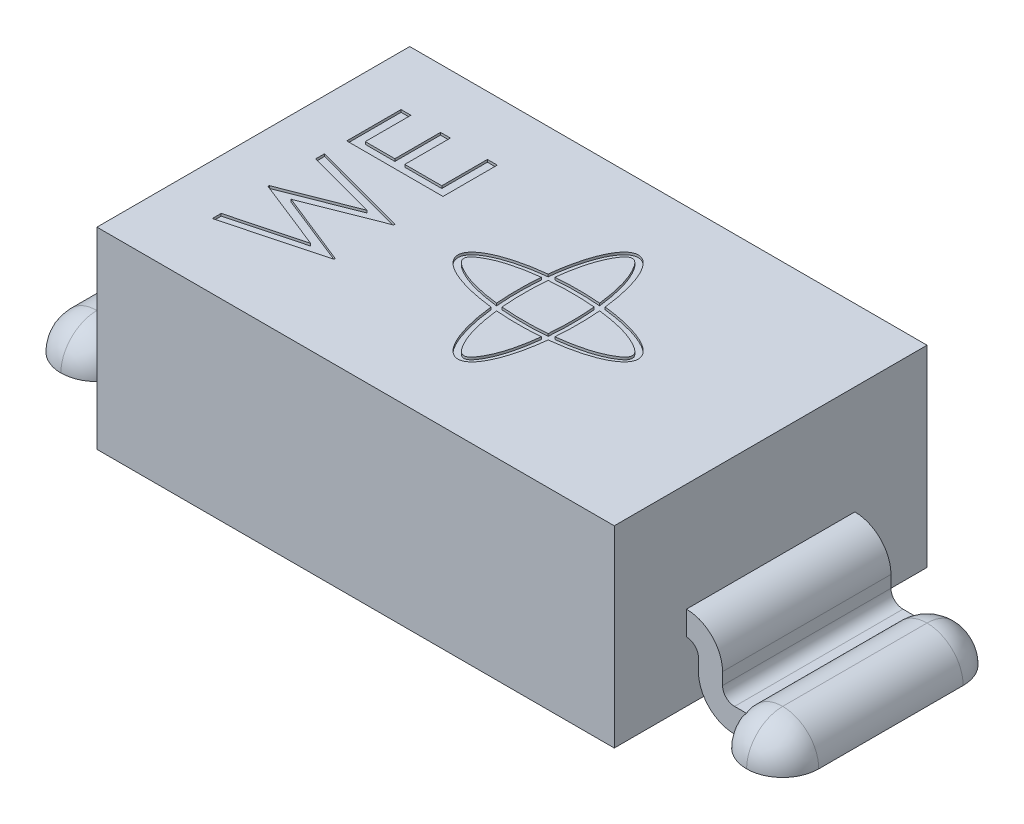
SolidWorks part; units mm, degrees
note: The reader was unsure of these and kept them because the rebuilt part matched: shared geometry of "Croquis3<2>".
ref_plane "Alzado" through (0, 0, 0) normal (0, 0, 1) x (1, 0, 0)
ref_plane "Planta" through (0, 0, 0) normal (0, 1, 0) x (1, 0, 0)
ref_plane "Vista lateral" through (0, 0, 0) normal (1, 0, 0) x (0, 0, -1)
sketch "Croquis1" plane through (0, 0, 0) normal (0, 1, 0) x (1, 0, 0)
  line L1 (-2.15, -1.3) -> (2.15, -1.3)
  line L2 (-2.15, -1.3) -> (-2.15, 1.3)
  line L3 (-2.15, 1.3) -> (2.15, 1.3)
  line L4 (2.15, -1.3) -> (2.15, 1.3)
  line L5 (-2.15, -1.3) -> (2.15, 1.3) construction
  line L6 (-2.15, 1.3) -> (2.15, -1.3) construction
  point P0 (0, 0)
  dimension "D1" = 4.3
  dimension "D2" = 2.6
extrude "Saliente-Extruir1" add sketch "Croquis1" along normal blind 1.6
sketch "Croquis2" plane through (0, 0, 0) normal (1, 0, 0) x (0, 0, -1)
  line L0 (-1.3, 1.6) -> (1.3, 1.6) construction
  line L1 (-0.7, 0.5) -> (0.7, 0.5)
  line L2 (-0.7, 0.5) -> (-0.7, 0.7)
  line L3 (-0.7, 0.7) -> (0.7, 0.7)
  line L4 (0.7, 0.5) -> (0.7, 0.7)
  line L5 (-0.7, 0.5) -> (0.7, 0.7) construction
  line L6 (-0.7, 0.7) -> (0.7, 0.5) construction
  point P0 (0, 0.6)
  dimension "D1" = 0.9
  dimension "D2" = 1.4
  dimension "D3" = 0.2
extrude "Cortar-Extruir1" cut sketch "Croquis2" against normal through all both and the other way through all
sketch "Croquis3" plane through (0, 0, 0) normal (0, 0, 1) x (1, 0, 0)
  line L0 (2.15, 0.5) -> (-2.15, 0.5)
  line L1 (-2.55, 0.2) -> (-3, 0.2)
  line L2 (2.25, 0.4) -> (2.25, 0.3)
  line L3 (2.55, 0) -> (3, 0)
  line L4 (0, 0) -> (0, 0.5) construction
  line L5 (-2.55, 0) -> (-3, 0)
  line L6 (-2.25, 0.4) -> (-2.25, 0.3)
  line L7 (-2.45, 0.4) -> (-2.45, 0.3)
  line L8 (2.15, 0.7) -> (-2.15, 0.7)
  line L9 (2.45, 0.4) -> (2.45, 0.3)
  line L10 (2.55, 0.2) -> (3, 0.2)
  line L11 (-3, 0) -> (-3, 0.2)
  line L12 (3, 0) -> (3, 0.2)
  arc A0 (2.15, 0.5) -> (2.25, 0.4) centre (2.15, 0.4) cw
  arc A1 (2.25, 0.3) -> (2.55, 0) centre (2.55, 0.3) ccw
  arc A2 (-2.25, 0.3) -> (-2.55, 0) centre (-2.55, 0.3) cw
  arc A3 (-2.15, 0.5) -> (-2.25, 0.4) centre (-2.15, 0.4) ccw
  arc A4 (-2.45, 0.3) -> (-2.55, 0.2) centre (-2.55, 0.3) cw
  arc A5 (-2.15, 0.7) -> (-2.45, 0.4) centre (-2.15, 0.4) ccw
  arc A6 (2.15, 0.7) -> (2.45, 0.4) centre (2.15, 0.4) cw
  arc A7 (2.45, 0.3) -> (2.55, 0.2) centre (2.55, 0.3) ccw
  point P3 (0, 0.5)
  dimension "D3" = 0.1
  dimension "D1" = 6
  dimension "D2" = 0.2
extrude "Saliente-Extruir2" add sketch "Croquis3" along normal mid plane 1.4 separate body
sketch "Croquis4" plane through (0, 0, 0) normal (0, 1, 0) x (1, 0, 0)
  line L0 (-2.85, 0) -> (0, 0) construction
  line L1 (-2.55, 0.9) -> (-3.15, 0.9)
  line L2 (-2.55, 0.9) -> (-2.55, -0.9)
  line L3 (-2.55, -0.9) -> (-3.15, -0.9)
  line L4 (-3.15, 0.9) -> (-3.15, -0.9)
  line L5 (-2.55, 0.9) -> (-3.15, -0.9) construction
  line L6 (-2.55, -0.9) -> (-3.15, 0.9) construction
  line L7 (0, 0) -> (0, -1.3) construction
  line L8 (-2.15, -1.3) -> (2.15, -1.3) construction
  line L9 (2.55, -0.9) -> (3.15, -0.9)
  line L10 (3.15, 0.9) -> (3.15, -0.9)
  line L11 (2.55, 0.9) -> (3.15, 0.9)
  line L12 (2.55, 0.9) -> (2.55, -0.9)
  point P0 (-2.85, 0)
  dimension "D1" = 0.6
  dimension "D2" = 1.8
extrude "Saliente-Extruir3" add sketch "Croquis4" along normal blind 0.3 separate body
fillet "Redondeo1" radius 0.3 2 edges at (-3.15, 0.3, 0) (-2.55, 0.3, 0)
fillet "Redondeo2" radius 0.3 2 edges at (3.15, 0.3, 0) (2.55, 0.3, 0)
extrude "Cortar-Extruir2" cut sketch "Croquis3<2>" against normal mid plane 1.4
sketch "Croquis3<2>" plane through (0, 0, 0) normal (0, 0, 1) x (1, 0, 0) same geometry as "Croquis3"
sketch "Croquis5" plane through (0, 1.6, 0) normal (0, 1, 0) x (1, 0, 0)
  line L0 (1.05, 0) -> (-0.45, 0) construction
  line L1 (0.3, -0.25) -> (0.3, 0.25) construction
  line L3 (-1.7325, -0.759) -> (-1.7325, -0.6848)
  line L4 (-1.7325, -0.6848) -> (-1.1458, -0.5282)
  line L5 (-1.1458, -0.5282) -> (-1.7325, -0.2954)
  line L6 (-1.7325, -0.2954) -> (-1.7325, -0.2849)
  line L7 (-1.7325, -0.2849) -> (-1.1498, -0.0564)
  line L8 (-1.1498, -0.0564) -> (-1.7325, 0.101)
  line L9 (-1.7325, 0.101) -> (-1.7325, 0.1744)
  line L10 (-1.7325, 0.1744) -> (-0.9325, -0.0413)
  line L11 (-0.9325, -0.0413) -> (-0.9325, -0.0516)
  line L12 (-0.9325, -0.0516) -> (-1.5443, -0.2923)
  line L13 (-1.5443, -0.2923) -> (-0.9325, -0.5359)
  line L14 (-0.9325, -0.5359) -> (-0.9325, -0.5462)
  line L15 (-0.9325, -0.5462) -> (-1.7325, -0.759)
  line L16 (-1.7325, 0.359) -> (-1.7325, 0.8103)
  line L17 (-1.7325, 0.8103) -> (-1.6504, 0.8103)
  line L18 (-1.6504, 0.8103) -> (-1.6504, 0.4308)
  line L19 (-1.6504, 0.4308) -> (-1.4043, 0.4308)
  line L20 (-1.4043, 0.4308) -> (-1.4043, 0.8103)
  line L21 (-1.4043, 0.8103) -> (-1.3222, 0.8103)
  line L22 (-1.3222, 0.8103) -> (-1.3222, 0.4308)
  line L23 (-1.3222, 0.4308) -> (-1.0145, 0.4308)
  line L24 (-1.0145, 0.4308) -> (-1.0145, 0.8103)
  line L25 (-1.0145, 0.8103) -> (-0.9325, 0.8103)
  line L26 (-0.9325, 0.8103) -> (-0.9325, 0.359)
  line L27 (-0.9325, 0.359) -> (-1.7325, 0.359)
  ellipse E0 centre (0.3, 0) end of major axis (-0.45, 0) minor radius 0.25 (0.0628, 0.2372) -> (0.0628, -0.2372) ccw
  ellipse E1 centre (0.3, 0) end of major axis (0.3, 0.75) minor radius 0.25 (0.0578, 0.1863) -> (0.0578, -0.1863) ccw
  ellipse E2 centre (0.3, 0) end of major axis (-0.45, 0) minor radius 0.25 (0.1137, -0.2422) -> (0.4863, -0.2422) ccw
  ellipse E3 centre (0.3, 0) end of major axis (0.3, 0.75) minor radius 0.25 (0.0628, -0.2372) -> (0.5372, -0.2372) ccw
  ellipse E4 centre (0.3, 0) end of major axis (-0.45, 0) minor radius 0.25 (0.5372, -0.2372) -> (0.5372, 0.2372) ccw
  ellipse E5 centre (0.3, 0) end of major axis (0.3, 0.75) minor radius 0.25 (0.5422, -0.1863) -> (0.5422, 0.1863) ccw
  ellipse E6 centre (0.3, 0) end of major axis (-0.45, 0) minor radius 0.25 (0.4863, 0.2422) -> (0.1137, 0.2422) ccw
  ellipse E7 centre (0.3, 0) end of major axis (0.3, 0.75) minor radius 0.25 (0.5372, 0.2372) -> (0.0628, 0.2372) ccw
  spline S0 degree 3 poles (0.1137, -0.2422) (0.1255, -0.3449) (0.1618, -0.5222) (0.2485, -0.6829) (0.3, -0.7086) (0.3515, -0.6829) (0.4382, -0.5222) (0.4745, -0.3449) (0.4863, -0.2422) knots 1.908725 1.908725 1.908725 1.908725 2.356194 2.748894 3.141593 3.534292 3.926991 4.37446 4.37446 4.37446 4.37446
  spline S1 degree 3 poles (0.0578, 0.1863) (0.0321, 0.1833) (-0.0689, 0.1694) (-0.2367, 0.1304) (-0.3829, 0.0515) (-0.4086, 0) (-0.3829, -0.0515) (-0.2222, -0.1382) (-0.0449, -0.1745) (0.0578, -0.1863) knots 5.04935 5.04935 5.04935 5.04935 5.161459 5.497787 5.890486 6.283185 6.675884 7.068583 7.516053 7.516053 7.516053 7.516053
  spline S2 degree 3 poles (0.1085, -0.1915) (0.1708, -0.1971) (0.3, -0.2029) (0.4292, -0.1971) (0.4915, -0.1915) knots 7.588701 7.588701 7.588701 7.588701 7.853982 8.119262 8.119262 8.119262 8.119262
  spline S3 degree 3 poles (0.1085, 0.1915) (0.1029, 0.1292) (0.0971, 0) (0.1029, -0.1292) (0.1085, -0.1915) knots 1.305515 1.305515 1.305515 1.305515 1.570796 1.836076 1.836076 1.836076 1.836076
  spline S4 degree 3 poles (0.4915, -0.1915) (0.4971, -0.1292) (0.5029, 0) (0.4971, 0.1292) (0.4915, 0.1915) knots 4.447109 4.447109 4.447109 4.447109 4.712389 4.977669 4.977669 4.977669 4.977669
  spline S5 degree 3 poles (0.5422, -0.1863) (0.6449, -0.1745) (0.8222, -0.1382) (0.9829, -0.0515) (1.0086, 0) (0.9829, 0.0515) (0.8222, 0.1382) (0.6449, 0.1745) (0.5422, 0.1863) knots 8.191911 8.191911 8.191911 8.191911 8.63938 9.032079 9.424778 9.817477 10.210176 10.657567 10.657567 10.657567 10.657567
  spline S6 degree 3 poles (0.4915, 0.1915) (0.4291, 0.1971) (0.3096, 0.2025) (0.1803, 0.1976) (0.1178, 0.1924) (0.1085, 0.1915) knots 10.730174 10.730174 10.730174 10.730174 10.995574 11.220426 11.259985 11.259985 11.259985 11.259985
  spline S7 degree 3 poles (0.4863, 0.2422) (0.4745, 0.3449) (0.4382, 0.5222) (0.3515, 0.6829) (0.3, 0.7086) (0.2485, 0.6829) (0.1618, 0.5222) (0.1255, 0.3449) (0.1137, 0.2422) knots 5.050318 5.050318 5.050318 5.050318 5.497787 5.890486 6.283185 6.675884 7.068583 7.516053 7.516053 7.516053 7.516053
  point P8 (0.3, 0)
  point P36 (0.3, 0)
extrude "Cortar-Extruir3" cut sketch "Croquis5" against normal blind 0.02
sketch "Croquis6" [suppressed] plane through (0, 1.6, 0) normal (0, 1, 0) x (1, 0, 0)
  line L5 (-1.8077, 0.5273) -> (-1.6126, 0.5273)
  line L6 (-1.5373, -0.4727) -> (-1.8077, -0.4727)
  line L7 (-1.8077, -0.4727) -> (-1.8077, 0.5273)
  line L8 (-1.7179, 0.4247) -> (-1.7179, 0.1042)
  line L9 (-1.7179, 0.1042) -> (-1.6577, 0.1042)
  line L10 (-1.5962, 0.4247) -> (-1.7179, 0.4247)
  line L11 (-1.7179, 0.0016) -> (-1.7179, -0.3702)
  line L12 (-1.7179, -0.3702) -> (-1.5901, -0.3702)
  line L13 (-1.6585, 0.0016) -> (-1.7179, 0.0016)
  line L14 (-0.9744, 0.2965) -> (-1.0641, 0.2965)
  line L15 (-1.1026, -0.2035) -> (-1.0128, -0.2035)
  line L16 (-0.8205, 0.0273) -> (-0.8205, 0.1298)
  line L17 (0.2125, 0.5529) -> (0.2308, 0.5529)
  line L18 (0.2308, 0.5529) -> (0.2308, -0.1394)
  line L19 (0.2308, -0.1394) -> (0.3462, -0.1394)
  line L20 (0.3462, -0.1394) -> (0.3462, -0.242)
  line L21 (0.3462, -0.242) -> (0.2308, -0.242)
  line L22 (0.2308, -0.242) -> (0.2308, -0.4727)
  line L23 (0.2308, -0.4727) -> (0.141, -0.4727)
  line L24 (0.141, -0.4727) -> (0.141, -0.242)
  line L25 (0.141, -0.242) -> (-0.3333, -0.242)
  line L26 (-0.3333, -0.242) -> (0.2125, 0.5529)
  line L27 (0.141, -0.1394) -> (0.141, 0.2949)
  line L28 (0.141, 0.2949) -> (-0.1571, -0.1394)
  line L29 (-0.1571, -0.1394) -> (0.141, -0.1394)
  line L30 (1.751, 0.5529) -> (1.7692, 0.5529)
  line L31 (1.7692, 0.5529) -> (1.7692, -0.1394)
  line L32 (1.7692, -0.1394) -> (1.8846, -0.1394)
  line L33 (1.8846, -0.1394) -> (1.8846, -0.242)
  line L34 (1.8846, -0.242) -> (1.7692, -0.242)
  line L35 (1.7692, -0.242) -> (1.7692, -0.4727)
  line L36 (1.7692, -0.4727) -> (1.6795, -0.4727)
  line L37 (1.6795, -0.4727) -> (1.6795, -0.242)
  line L38 (1.6795, -0.242) -> (1.2051, -0.242)
  line L39 (1.2051, -0.242) -> (1.751, 0.5529)
  line L40 (1.6795, -0.1394) -> (1.6795, 0.2949)
  line L41 (1.6795, 0.2949) -> (1.3814, -0.1394)
  line L42 (1.3814, -0.1394) -> (1.6795, -0.1394)
  spline S0 degree 3 poles (-1.6126, 0.5273) (-1.5941, 0.5274) (-1.5671, 0.5264) (-1.5324, 0.5236) (-1.5089, 0.5203) (-1.4871, 0.5164) (-1.4669, 0.5116) (-1.4484, 0.5059) (-1.4264, 0.4968) (-1.4013, 0.4832) (-1.3741, 0.4633) (-1.3508, 0.4388) (-1.3308, 0.4113) (-1.3149, 0.3809) (-1.2993, 0.3375) (-1.2947, 0.3028) (-1.2949, 0.2795) knots 0 0 0 0 0.121323 0.17668 0.228365 0.276868 0.321879 0.364099 0.403356 0.477968 0.550535 0.623584 0.698175 0.773354 0.847281 1 1 1 1
  spline S1 degree 3 poles (-1.2949, 0.2795) (-1.2947, 0.2578) (-1.2984, 0.2256) (-1.3109, 0.1848) (-1.3236, 0.1562) (-1.3402, 0.1299) (-1.3667, 0.0972) (-1.3925, 0.0781) (-1.4105, 0.0667) knots 0 0 0 0 0.256581 0.380552 0.503623 0.625739 0.747549 1 1 1 1
  spline S2 degree 3 poles (-1.4105, 0.0667) (-1.3887, 0.0587) (-1.3578, 0.0458) (-1.3217, 0.0232) (-1.2999, 0.0057) (-1.2812, -0.0132) (-1.2649, -0.0337) (-1.251, -0.0561) (-1.2391, -0.0803) (-1.2298, -0.1058) (-1.2203, -0.1418) (-1.2181, -0.17) (-1.2179, -0.1889) knots 0 0 0 0 0.202914 0.2903 0.370223 0.446384 0.521397 0.598291 0.676142 0.755529 0.834887 1 1 1 1
  spline S3 degree 3 poles (-1.2179, -0.1889) (-1.2181, -0.208) (-1.2204, -0.2366) (-1.2297, -0.273) (-1.2391, -0.2989) (-1.2515, -0.3237) (-1.2665, -0.3473) (-1.2844, -0.3696) (-1.3044, -0.3909) (-1.327, -0.41) (-1.3515, -0.427) (-1.378, -0.441) (-1.4062, -0.4527) (-1.4363, -0.4617) (-1.48, -0.4703) (-1.5141, -0.473) (-1.5373, -0.4727) knots 0 0 0 0 0.120335 0.17818 0.235235 0.292683 0.351186 0.410457 0.47172 0.533761 0.595739 0.657888 0.721295 0.786823 0.854686 1 1 1 1
  spline S4 degree 3 poles (-1.6577, 0.1042) (-1.6406, 0.1045) (-1.6159, 0.1045) (-1.5843, 0.1069) (-1.5632, 0.1087) (-1.5439, 0.1116) (-1.5266, 0.115) (-1.5108, 0.1186) (-1.4927, 0.1248) (-1.4721, 0.1339) (-1.4501, 0.148) (-1.4308, 0.1649) (-1.4144, 0.1843) (-1.4011, 0.2057) (-1.3885, 0.2365) (-1.3842, 0.2611) (-1.3846, 0.2777) knots 0 0 0 0 0.1397 0.202289 0.2606 0.31319 0.361739 0.405706 0.44554 0.518832 0.589778 0.658867 0.72843 0.797283 0.864815 1 1 1 1
  spline S5 degree 3 poles (-1.3846, 0.2777) (-1.3847, 0.2885) (-1.386, 0.3046) (-1.3916, 0.3249) (-1.3969, 0.3391) (-1.4042, 0.3521) (-1.4129, 0.3644) (-1.4234, 0.3755) (-1.4353, 0.3859) (-1.449, 0.3951) (-1.4645, 0.4032) (-1.482, 0.4097) (-1.5012, 0.4154) (-1.5223, 0.4194) (-1.554, 0.424) (-1.579, 0.4246) (-1.5962, 0.4247) knots 0 0 0 0 0.111818 0.164402 0.21587 0.266841 0.317479 0.369902 0.4234 0.479718 0.539241 0.602431 0.67103 0.744485 0.823454 1 1 1 1
  spline S6 degree 3 poles (-1.5901, -0.3702) (-1.5725, -0.3699) (-1.547, -0.3697) (-1.5143, -0.3676) (-1.4927, -0.3651) (-1.4728, -0.3624) (-1.4549, -0.3588) (-1.4388, -0.3547) (-1.4202, -0.3483) (-1.3991, -0.3384) (-1.3765, -0.3235) (-1.3564, -0.3056) (-1.3393, -0.285) (-1.3253, -0.2626) (-1.3117, -0.2311) (-1.3077, -0.2057) (-1.3077, -0.1889) knots 0 0 0 0 0.139739 0.201795 0.259822 0.312206 0.360773 0.40454 0.443698 0.516841 0.587874 0.657965 0.728969 0.799308 0.866636 1 1 1 1
  spline S7 degree 3 poles (-1.3077, -0.1889) (-1.3075, -0.1784) (-1.3091, -0.1628) (-1.3137, -0.1428) (-1.3182, -0.1283) (-1.3246, -0.1145) (-1.3322, -0.1012) (-1.341, -0.0882) (-1.3548, -0.0719) (-1.3748, -0.0531) (-1.4139, -0.0277) (-1.4477, -0.0157) (-1.4714, -0.0102) knots 0 0 0 0 0.119602 0.177503 0.235143 0.292133 0.350871 0.410098 0.470732 0.594829 0.722579 1 1 1 1
  spline S8 degree 3 poles (-1.4714, -0.0102) (-1.4819, -0.0078) (-1.499, -0.0053) (-1.5236, -0.0028) (-1.5457, -0.0013) (-1.5704, 0.0002) (-1.6082, 0.0011) (-1.6379, 0.0018) (-1.6585, 0.0016) knots 0 0 0 0 0.171953 0.277057 0.394731 0.526177 0.671345 1 1 1 1
  spline S9 degree 3 poles (-1.0641, 0.2965) (-1.0599, 0.3163) (-1.0509, 0.3448) (-1.0362, 0.381) (-1.0232, 0.4056) (-1.0091, 0.4287) (-0.9929, 0.4497) (-0.9754, 0.4693) (-0.956, 0.4866) (-0.9357, 0.5023) (-0.9141, 0.5157) (-0.8918, 0.5272) (-0.8685, 0.5367) (-0.8441, 0.5439) (-0.8102, 0.5509) (-0.7841, 0.5531) (-0.7664, 0.5529) knots 0 0 0 0 0.141977 0.208985 0.273957 0.336889 0.398745 0.460116 0.520825 0.580994 0.640152 0.698622 0.757271 0.816427 0.876254 1 1 1 1
  spline S10 degree 3 poles (-0.7664, 0.5529) (-0.7406, 0.5531) (-0.7021, 0.5486) (-0.653, 0.5334) (-0.6182, 0.5178) (-0.5859, 0.4986) (-0.5571, 0.4758) (-0.5323, 0.4497) (-0.5114, 0.4209) (-0.4951, 0.3902) (-0.4791, 0.3482) (-0.4744, 0.315) (-0.4744, 0.2931) knots 0 0 0 0 0.17854 0.266093 0.354631 0.441886 0.525747 0.608114 0.690197 0.770821 0.848326 1 1 1 1
  spline S11 degree 3 poles (-0.4744, 0.2931) (-0.4744, 0.2725) (-0.4775, 0.2417) (-0.4902, 0.2032) (-0.503, 0.1763) (-0.5197, 0.1513) (-0.5473, 0.1193) (-0.5728, 0.0993) (-0.5911, 0.0874) knots 0 0 0 0 0.250608 0.37063 0.490072 0.610375 0.734313 1 1 1 1
  spline S12 degree 3 poles (-0.5911, 0.0874) (-0.5698, 0.0779) (-0.5293, 0.0542) (-0.4966, 0.0205) (-0.4828, 0.002) knots 0 0 0 0 0.503009 1 1 1 1
  spline S13 degree 3 poles (-0.4828, 0.002) (-0.4728, -0.0107) (-0.4603, -0.0313) (-0.446, -0.0599) (-0.4376, -0.0819) (-0.4312, -0.1045) (-0.425, -0.1356) (-0.4232, -0.1596) (-0.4231, -0.1756) knots 0 0 0 0 0.254173 0.378112 0.501712 0.623986 0.747096 1 1 1 1
  spline S14 degree 3 poles (-0.4231, -0.1756) (-0.4229, -0.2036) (-0.429, -0.2456) (-0.448, -0.2992) (-0.4681, -0.3378) (-0.4926, -0.3739) (-0.5218, -0.4062) (-0.5553, -0.434) (-0.5927, -0.4572) (-0.6332, -0.4757) (-0.6917, -0.4932) (-0.7378, -0.4986) (-0.769, -0.4984) knots 0 0 0 0 0.158922 0.239619 0.322609 0.406035 0.487602 0.569685 0.653036 0.737436 0.822478 1 1 1 1
  spline S15 degree 3 poles (-0.769, -0.4984) (-0.79, -0.4981) (-0.8212, -0.4965) (-0.8612, -0.4882) (-0.8894, -0.48) (-0.9162, -0.4696) (-0.9416, -0.4566) (-0.9657, -0.4414) (-0.9883, -0.4237) (-1.0094, -0.4039) (-1.0285, -0.3817) (-1.0458, -0.3574) (-1.061, -0.3308) (-1.0746, -0.3022) (-1.0899, -0.26) (-1.0985, -0.2266) (-1.1026, -0.2035) knots 0 0 0 0 0.128963 0.190377 0.250092 0.308548 0.366398 0.424542 0.48317 0.542243 0.601739 0.662506 0.724856 0.789128 0.856346 1 1 1 1
  spline S16 degree 3 poles (-1.0128, -0.2035) (-1.0083, -0.2185) (-1.0015, -0.2404) (-0.9894, -0.2675) (-0.9799, -0.2856) (-0.97, -0.3022) (-0.9555, -0.3215) (-0.9435, -0.3345) (-0.9345, -0.3417) knots 0 0 0 0 0.291316 0.425966 0.55216 0.671527 0.786122 1 1 1 1
  spline S17 degree 3 poles (-0.9345, -0.3417) (-0.9235, -0.3506) (-0.9059, -0.3625) (-0.8803, -0.3752) (-0.8598, -0.3825) (-0.8384, -0.3886) (-0.8075, -0.3941) (-0.7837, -0.396) (-0.7674, -0.3958) knots 0 0 0 0 0.236178 0.355663 0.475904 0.600127 0.728608 1 1 1 1
  spline S18 degree 3 poles (-0.7674, -0.3958) (-0.7491, -0.3959) (-0.7223, -0.3938) (-0.6877, -0.3875) (-0.6638, -0.3804) (-0.6413, -0.3716) (-0.6203, -0.3605) (-0.6007, -0.3476) (-0.5826, -0.3329) (-0.5663, -0.3167) (-0.552, -0.2999) (-0.5398, -0.2824) (-0.53, -0.2641) (-0.5222, -0.2451) (-0.5151, -0.2186) (-0.5125, -0.1981) (-0.5128, -0.1843) knots 0 0 0 0 0.148752 0.218403 0.28576 0.350598 0.414964 0.478069 0.541761 0.60435 0.664075 0.721464 0.777587 0.832644 0.887844 1 1 1 1
  spline S19 degree 3 poles (-0.5128, -0.1843) (-0.5129, -0.1657) (-0.5171, -0.1376) (-0.5318, -0.1027) (-0.5471, -0.0778) (-0.5657, -0.0547) (-0.5876, -0.0341) (-0.6127, -0.0171) (-0.6359, -0.0054) (-0.6564, 0.0027) (-0.6739, 0.008) (-0.6936, 0.0125) (-0.7151, 0.0167) (-0.7386, 0.0203) (-0.7739, 0.0244) (-0.8015, 0.0263) (-0.8205, 0.0273) knots 0 0 0 0 0.133485 0.201035 0.271234 0.34288 0.413836 0.485977 0.56023 0.599884 0.644055 0.691892 0.744688 0.801492 0.862858 1 1 1 1
  spline S20 degree 3 poles (-0.8205, 0.1298) (-0.7963, 0.1295) (-0.7606, 0.1329) (-0.7147, 0.1423) (-0.6831, 0.1529) (-0.6544, 0.1651) (-0.6294, 0.1793) (-0.6086, 0.1952) (-0.5921, 0.2128) (-0.5797, 0.2318) (-0.5675, 0.258) (-0.5642, 0.2794) (-0.5641, 0.2935) knots 0 0 0 0 0.215787 0.318027 0.417574 0.51165 0.596162 0.672935 0.74367 0.810677 0.874059 1 1 1 1
  spline S21 degree 3 poles (-0.5641, 0.2935) (-0.5639, 0.3039) (-0.5659, 0.3193) (-0.5719, 0.339) (-0.578, 0.3532) (-0.5862, 0.3668) (-0.5961, 0.3798) (-0.6078, 0.3923) (-0.6212, 0.4039) (-0.6356, 0.415) (-0.6514, 0.4244) (-0.6681, 0.4324) (-0.6857, 0.4391) (-0.7043, 0.444) (-0.7308, 0.4489) (-0.7513, 0.4503) (-0.7652, 0.4504) knots 0 0 0 0 0.109966 0.163247 0.218076 0.273301 0.330909 0.390995 0.454176 0.518862 0.583311 0.648517 0.715031 0.782502 0.852323 1 1 1 1
  spline S22 degree 3 poles (-0.7652, 0.4504) (-0.7874, 0.4504) (-0.8202, 0.4464) (-0.8607, 0.4315) (-0.8835, 0.4186) (-0.9003, 0.4058) (-0.9123, 0.3946) (-0.9242, 0.3822) (-0.935, 0.3678) (-0.9459, 0.3524) (-0.9596, 0.3287) (-0.9687, 0.3098) (-0.9744, 0.2965) knots 0 0 0 0 0.239685 0.351816 0.463766 0.520818 0.579448 0.640604 0.705298 0.773634 0.844669 1 1 1 1
  spline S23 degree 3 poles (0.4359, 0.0269) (0.4358, 0.058) (0.4369, 0.1034) (0.4416, 0.162) (0.4462, 0.2017) (0.4518, 0.2387) (0.4593, 0.2728) (0.4678, 0.3041) (0.4777, 0.3328) (0.4888, 0.3592) (0.5009, 0.3839) (0.5145, 0.4068) (0.5288, 0.4283) (0.5443, 0.448) (0.5607, 0.4662) (0.5785, 0.4824) (0.5972, 0.4972) (0.617, 0.5102) (0.6371, 0.5217) (0.6579, 0.5314) (0.6794, 0.5391) (0.7013, 0.5455) (0.7315, 0.5513) (0.7547, 0.553) (0.7702, 0.5529) knots 0 0 0 0 0.133246 0.194313 0.251279 0.304513 0.354235 0.400481 0.443411 0.484015 0.523252 0.561042 0.5979 0.633518 0.668314 0.702496 0.736685 0.770293 0.803437 0.835913 0.86846 0.900847 0.933467 1 1 1 1
  spline S24 degree 3 poles (0.7702, 0.5529) (0.786, 0.553) (0.8096, 0.5514) (0.8402, 0.5454) (0.8624, 0.5392) (0.8842, 0.5314) (0.9053, 0.5216) (0.9259, 0.5103) (0.9457, 0.497) (0.965, 0.4821) (0.9831, 0.4653) (1.0001, 0.4468) (1.0163, 0.4267) (1.0312, 0.4046) (1.0454, 0.3809) (1.058, 0.3553) (1.0702, 0.3281) (1.0808, 0.2986) (1.0903, 0.2669) (1.098, 0.2328) (1.1044, 0.1963) (1.1093, 0.1573) (1.1143, 0.1006) (1.1151, 0.0568) (1.1154, 0.0269) knots 0 0 0 0 0.067194 0.099862 0.132567 0.165151 0.197913 0.231319 0.265083 0.299255 0.334399 0.369943 0.406284 0.444064 0.482998 0.523354 0.565537 0.609613 0.656391 0.705885 0.758325 0.813832 0.872795 1 1 1 1
  spline S25 degree 3 poles (1.1154, 0.0269) (1.1151, -0.0029) (1.1143, -0.0466) (1.1093, -0.1029) (1.1046, -0.1417) (1.0982, -0.178) (1.0903, -0.212) (1.0816, -0.2437) (1.0708, -0.2729) (1.0589, -0.3) (1.046, -0.3253) (1.0323, -0.3491) (1.0172, -0.3711) (1.0012, -0.3915) (0.9839, -0.4099) (0.9657, -0.4268) (0.9464, -0.4419) (0.9263, -0.455) (0.9057, -0.4668) (0.8844, -0.4763) (0.8627, -0.4845) (0.8404, -0.4907) (0.8096, -0.4965) (0.7861, -0.4986) (0.7702, -0.4984) knots 0 0 0 0 0.126773 0.185516 0.240765 0.29298 0.34225 0.388919 0.432776 0.474628 0.514775 0.553606 0.591426 0.628028 0.663804 0.698984 0.733591 0.767628 0.801208 0.834264 0.866981 0.89972 0.932702 1 1 1 1
  spline S26 degree 3 poles (0.7702, -0.4984) (0.7547, -0.4984) (0.7315, -0.4968) (0.7014, -0.4909) (0.6796, -0.4848) (0.6582, -0.4773) (0.6376, -0.4675) (0.6176, -0.4563) (0.598, -0.4435) (0.5795, -0.4288) (0.5617, -0.4126) (0.5453, -0.3944) (0.5299, -0.3746) (0.5154, -0.3532) (0.502, -0.3301) (0.4896, -0.3053) (0.4783, -0.2786) (0.4682, -0.2497) (0.4593, -0.2183) (0.4523, -0.1839) (0.4463, -0.147) (0.4415, -0.1074) (0.437, -0.0492) (0.4358, -0.0041) (0.4359, 0.0269) knots 0 0 0 0 0.066622 0.099285 0.131361 0.163585 0.196104 0.228902 0.262158 0.295991 0.330218 0.36506 0.400951 0.43762 0.475708 0.515381 0.556414 0.599765 0.646424 0.696431 0.749782 0.806573 0.867436 1 1 1 1
  spline S27 degree 3 poles (0.5256, 0.0273) (0.5254, 0.0014) (0.5266, -0.0363) (0.5298, -0.0848) (0.5329, -0.1174) (0.5374, -0.1475) (0.5424, -0.1751) (0.5486, -0.2002) (0.5559, -0.223) (0.5642, -0.2437) (0.5732, -0.2631) (0.583, -0.2812) (0.5939, -0.2979) (0.6057, -0.3133) (0.6183, -0.3276) (0.632, -0.3404) (0.651, -0.3558) (0.6761, -0.3716) (0.7178, -0.39) (0.7512, -0.3958) (0.7732, -0.3958) knots 0 0 0 0 0.141584 0.205926 0.265301 0.320597 0.371817 0.41879 0.461699 0.502134 0.540804 0.578181 0.614297 0.649678 0.684299 0.718359 0.752081 0.817652 0.879722 1 1 1 1
  spline S28 degree 3 poles (0.7732, -0.3958) (0.7954, -0.3962) (0.8286, -0.3901) (0.8701, -0.3723) (0.8947, -0.3567) (0.9134, -0.3417) (0.9268, -0.329) (0.9391, -0.3147) (0.9508, -0.2993) (0.9615, -0.2825) (0.9748, -0.2577) (0.9829, -0.2378) (0.9878, -0.2241) knots 0 0 0 0 0.225394 0.339595 0.459675 0.521735 0.583926 0.648174 0.713881 0.781004 0.851451 1 1 1 1
  spline S29 degree 3 poles (0.9878, -0.2241) (0.994, -0.2061) (1.0029, -0.1782) (1.011, -0.1395) (1.0166, -0.1088) (1.0204, -0.0767) (1.0246, -0.0312) (1.0256, 0.0036) (1.0256, 0.0273) knots 0 0 0 0 0.224542 0.342503 0.464324 0.590756 0.722227 1 1 1 1
  spline S30 degree 3 poles (1.0256, 0.0273) (1.0252, 0.0508) (1.0251, 0.0853) (1.021, 0.13) (1.0176, 0.1611) (1.0126, 0.1904) (1.0073, 0.2183) (1.0001, 0.2443) (0.9924, 0.2688) (0.9836, 0.2916) (0.9739, 0.3128) (0.9635, 0.3324) (0.9523, 0.3505) (0.9403, 0.3671) (0.9272, 0.3818) (0.9136, 0.3952) (0.8945, 0.4105) (0.8695, 0.426) (0.8284, 0.4451) (0.795, 0.4501) (0.7732, 0.4504) knots 0 0 0 0 0.128486 0.188175 0.245106 0.299448 0.350823 0.399942 0.446672 0.491255 0.533376 0.573853 0.612526 0.649597 0.685532 0.720106 0.753838 0.818925 0.880493 1 1 1 1
  spline S31 degree 3 poles (0.7732, 0.4504) (0.7512, 0.4501) (0.7174, 0.4451) (0.676, 0.4261) (0.6511, 0.4104) (0.632, 0.3955) (0.6185, 0.3825) (0.6059, 0.3683) (0.5943, 0.3528) (0.5834, 0.3361) (0.5734, 0.3181) (0.5644, 0.2987) (0.5561, 0.2779) (0.5488, 0.2552) (0.5428, 0.2301) (0.5372, 0.2026) (0.5332, 0.1724) (0.5297, 0.1397) (0.5266, 0.0911) (0.5254, 0.0533) (0.5256, 0.0273) knots 0 0 0 0 0.120883 0.182755 0.247811 0.281299 0.315088 0.349702 0.384857 0.420966 0.458511 0.497175 0.537602 0.580503 0.627468 0.678388 0.733983 0.793747 0.857714 1 1 1 1
extrude "Cortar-Extruir4" [suppressed] cut sketch "Croquis6" against normal blind 0.02
sketch "Croquis7" [suppressed] plane through (0, 1.6, 0) normal (0, 1, 0) x (1, 0, 0)
  line L1 (-1.7421, -0.3966) -> (-1.6407, -0.3358)
  line L2 (-1.0498, 0.3995) -> (-1.1472, 0.3257)
  line L3 (-0.9114, -0.3966) -> (-0.8099, -0.3358)
  line L4 (-0.2191, 0.3995) -> (-0.3164, 0.3257)
  line L5 (0.0886, 0.2949) -> (-0.0191, 0.2949)
  line L6 (-0.0652, -0.3051) -> (0.0425, -0.3051)
  line L7 (0.2732, -0.0281) -> (0.2732, 0.0949)
  line L8 (1.5129, 0.6026) -> (1.5348, 0.6026)
  line L9 (1.5348, 0.6026) -> (1.5348, -0.2281)
  line L10 (1.5348, -0.2281) -> (1.6732, -0.2281)
  line L11 (1.6732, -0.2281) -> (1.6732, -0.3512)
  line L12 (1.6732, -0.3512) -> (1.5348, -0.3512)
  line L13 (1.5348, -0.3512) -> (1.5348, -0.6281)
  line L14 (1.5348, -0.6281) -> (1.4271, -0.6281)
  line L15 (1.4271, -0.6281) -> (1.4271, -0.3512)
  line L16 (1.4271, -0.3512) -> (0.8579, -0.3512)
  line L17 (0.8579, -0.3512) -> (1.5129, 0.6026)
  line L18 (1.4271, -0.2281) -> (1.4271, 0.293)
  line L19 (1.4271, 0.293) -> (1.0694, -0.2281)
  line L20 (1.0694, -0.2281) -> (1.4271, -0.2281)
  spline S0 degree 3 poles (-1.6407, -0.3358) (-1.6231, -0.3663) (-1.5954, -0.4091) (-1.5518, -0.4575) (-1.5192, -0.4859) (-1.4855, -0.5083) (-1.4392, -0.5293) (-1.4019, -0.5359) (-1.3772, -0.5358) knots 0 0 0 0 0.304646 0.438547 0.562322 0.677433 0.786897 1 1 1 1
  spline S1 degree 3 poles (-1.3772, -0.5358) (-1.3564, -0.536) (-1.3253, -0.5323) (-1.2853, -0.5208) (-1.257, -0.5085) (-1.2306, -0.4937) (-1.2074, -0.4757) (-1.1874, -0.4556) (-1.171, -0.4332) (-1.1584, -0.4091) (-1.1455, -0.3762) (-1.1425, -0.3498) (-1.1421, -0.3325) knots 0 0 0 0 0.18093 0.270088 0.360156 0.448343 0.532666 0.613834 0.693982 0.772716 0.849335 1 1 1 1
  spline S2 degree 3 poles (-1.1421, -0.3325) (-1.142, -0.3121) (-1.1502, -0.2697) (-1.1721, -0.2326) (-1.1852, -0.2147) knots 0 0 0 0 0.477158 1 1 1 1
  spline S3 degree 3 poles (-1.1852, -0.2147) (-1.1962, -0.2001) (-1.2149, -0.178) (-1.244, -0.1497) (-1.2693, -0.1261) (-1.2982, -0.102) (-1.3416, -0.0665) (-1.3771, -0.0409) (-1.4015, -0.0233) knots 0 0 0 0 0.18953 0.299198 0.418926 0.548376 0.688136 1 1 1 1
  spline S4 degree 3 poles (-1.4015, -0.0233) (-1.4258, -0.0063) (-1.4598, 0.0189) (-1.5022, 0.0517) (-1.5287, 0.0731) (-1.5515, 0.0925) (-1.5751, 0.1136) (-1.5899, 0.1297) (-1.5982, 0.1399) knots 0 0 0 0 0.347082 0.495568 0.628357 0.74552 0.845831 1 1 1 1
  spline S5 degree 3 poles (-1.5982, 0.1399) (-1.6088, 0.1536) (-1.6236, 0.1747) (-1.6394, 0.2048) (-1.6485, 0.2276) (-1.6563, 0.2506) (-1.6632, 0.2822) (-1.6653, 0.3064) (-1.6652, 0.3226) knots 0 0 0 0 0.262559 0.388264 0.512667 0.633722 0.755394 1 1 1 1
  spline S6 degree 3 poles (-1.6652, 0.3226) (-1.6653, 0.3477) (-1.6605, 0.3851) (-1.6446, 0.4321) (-1.628, 0.4652) (-1.6067, 0.4953) (-1.582, 0.523) (-1.5526, 0.5462) (-1.5203, 0.5665) (-1.4849, 0.5824) (-1.4352, 0.5985) (-1.3957, 0.6023) (-1.3695, 0.6026) knots 0 0 0 0 0.16578 0.24628 0.327461 0.408797 0.489715 0.571376 0.655523 0.741019 0.826547 1 1 1 1
  spline S7 degree 3 poles (-1.3695, 0.6026) (-1.3415, 0.6027) (-1.2993, 0.5975) (-1.2461, 0.5788) (-1.2141, 0.563) (-1.189, 0.5471) (-1.1699, 0.5327) (-1.1505, 0.5161) (-1.1307, 0.4973) (-1.1108, 0.4761) (-1.083, 0.4439) (-1.0629, 0.4179) (-1.0498, 0.3995) knots 0 0 0 0 0.213252 0.31883 0.426794 0.483646 0.543604 0.608308 0.677127 0.750686 0.828713 1 1 1 1
  spline S8 degree 3 poles (-1.1472, 0.3257) (-1.1583, 0.3404) (-1.1753, 0.3611) (-1.1978, 0.3869) (-1.2137, 0.4032) (-1.2286, 0.4178) (-1.2431, 0.4303) (-1.2569, 0.4409) (-1.2742, 0.4521) (-1.2961, 0.4633) (-1.3329, 0.476) (-1.3621, 0.4794) (-1.3816, 0.4796) knots 0 0 0 0 0.189629 0.274184 0.352183 0.423199 0.488551 0.548473 0.60144 0.701198 0.799592 1 1 1 1
  spline S9 degree 3 poles (-1.3816, 0.4796) (-1.4054, 0.4799) (-1.4405, 0.4748) (-1.4824, 0.4558) (-1.5086, 0.4365) (-1.5304, 0.4136) (-1.5517, 0.3784) (-1.5575, 0.3478) (-1.5575, 0.3276) knots 0 0 0 0 0.275903 0.402371 0.528414 0.650356 0.765895 1 1 1 1
  spline S10 degree 3 poles (-1.5575, 0.3276) (-1.5579, 0.3147) (-1.555, 0.2955) (-1.5485, 0.2704) (-1.5409, 0.2515) (-1.5303, 0.2325) (-1.5107, 0.2048) (-1.4919, 0.1856) (-1.4784, 0.1726) knots 0 0 0 0 0.214746 0.322939 0.434116 0.553412 0.686073 1 1 1 1
  spline S11 degree 3 poles (-1.4784, 0.1726) (-1.4723, 0.1669) (-1.461, 0.1577) (-1.4431, 0.1443) (-1.4248, 0.1304) (-1.4028, 0.1143) (-1.3665, 0.0884) (-1.3377, 0.0676) (-1.3171, 0.0531) knots 0 0 0 0 0.124952 0.218094 0.333502 0.468789 0.624938 1 1 1 1
  spline S12 degree 3 poles (-1.3171, 0.0531) (-1.2919, 0.0348) (-1.2554, 0.008) (-1.2105, -0.0292) (-1.1812, -0.0554) (-1.1548, -0.0806) (-1.1317, -0.1052) (-1.1116, -0.1289) (-1.0899, -0.1592) (-1.0678, -0.1965) (-1.0428, -0.2563) (-1.0345, -0.3033) (-1.0345, -0.3341) knots 0 0 0 0 0.187773 0.272396 0.351321 0.424335 0.491909 0.554233 0.611268 0.716348 0.81454 1 1 1 1
  spline S13 degree 3 poles (-1.0345, -0.3341) (-1.0341, -0.3555) (-1.0376, -0.387) (-1.0478, -0.4279) (-1.0591, -0.457) (-1.0729, -0.4854) (-1.0905, -0.5122) (-1.1108, -0.5382) (-1.1341, -0.5626) (-1.1596, -0.5851) (-1.1866, -0.605) (-1.2151, -0.6216) (-1.2449, -0.6352) (-1.2761, -0.6458) (-1.32, -0.6562) (-1.3542, -0.659) (-1.3772, -0.6589) knots 0 0 0 0 0.121775 0.18092 0.240256 0.300114 0.361146 0.423501 0.488669 0.553954 0.617581 0.680238 0.742187 0.804663 0.868259 1 1 1 1
  spline S14 degree 3 poles (-1.3772, -0.6589) (-1.3953, -0.659) (-1.422, -0.6568) (-1.4571, -0.6509) (-1.4823, -0.644) (-1.507, -0.6356) (-1.5311, -0.6253) (-1.5545, -0.6129) (-1.5774, -0.5988) (-1.5997, -0.5823) (-1.6213, -0.5631) (-1.6428, -0.5417) (-1.6636, -0.5176) (-1.6841, -0.4911) (-1.7114, -0.4511) (-1.7301, -0.419) (-1.7421, -0.3966) knots 0 0 0 0 0.113696 0.169178 0.224159 0.27872 0.333794 0.389241 0.445822 0.503704 0.564294 0.627975 0.695038 0.765373 0.839611 1 1 1 1
  spline S15 degree 3 poles (-0.8099, -0.3358) (-0.7924, -0.3663) (-0.7646, -0.4091) (-0.721, -0.4575) (-0.6885, -0.4859) (-0.6548, -0.5083) (-0.6085, -0.5293) (-0.5712, -0.5359) (-0.5465, -0.5358) knots 0 0 0 0 0.304646 0.438547 0.562322 0.677433 0.786897 1 1 1 1
  spline S16 degree 3 poles (-0.5465, -0.5358) (-0.5256, -0.536) (-0.4945, -0.5323) (-0.4546, -0.5208) (-0.4262, -0.5085) (-0.3998, -0.4937) (-0.3766, -0.4757) (-0.3566, -0.4556) (-0.3402, -0.4332) (-0.3276, -0.4091) (-0.3147, -0.3762) (-0.3117, -0.3498) (-0.3114, -0.3325) knots 0 0 0 0 0.18093 0.270088 0.360156 0.448343 0.532666 0.613834 0.693982 0.772716 0.849335 1 1 1 1
  spline S17 degree 3 poles (-0.3114, -0.3325) (-0.3113, -0.3121) (-0.3195, -0.2697) (-0.3413, -0.2326) (-0.3544, -0.2147) knots 0 0 0 0 0.477158 1 1 1 1
  spline S18 degree 3 poles (-0.3544, -0.2147) (-0.3655, -0.2001) (-0.3842, -0.178) (-0.4132, -0.1497) (-0.4385, -0.1261) (-0.4674, -0.102) (-0.5109, -0.0665) (-0.5463, -0.0409) (-0.5707, -0.0233) knots 0 0 0 0 0.18953 0.299198 0.418926 0.548376 0.688136 1 1 1 1
  spline S19 degree 3 poles (-0.5707, -0.0233) (-0.595, -0.0063) (-0.629, 0.0189) (-0.6715, 0.0517) (-0.6979, 0.0731) (-0.7207, 0.0925) (-0.7444, 0.1136) (-0.7591, 0.1297) (-0.7674, 0.1399) knots 0 0 0 0 0.347082 0.495568 0.628357 0.74552 0.845831 1 1 1 1
  spline S20 degree 3 poles (-0.7674, 0.1399) (-0.778, 0.1536) (-0.7928, 0.1747) (-0.8086, 0.2048) (-0.8178, 0.2276) (-0.8255, 0.2506) (-0.8325, 0.2822) (-0.8345, 0.3064) (-0.8345, 0.3226) knots 0 0 0 0 0.262559 0.388264 0.512667 0.633722 0.755394 1 1 1 1
  spline S21 degree 3 poles (-0.8345, 0.3226) (-0.8345, 0.3477) (-0.8298, 0.3851) (-0.8138, 0.4321) (-0.7973, 0.4652) (-0.7759, 0.4953) (-0.7512, 0.523) (-0.7218, 0.5462) (-0.6895, 0.5665) (-0.6542, 0.5824) (-0.6044, 0.5985) (-0.565, 0.6023) (-0.5388, 0.6026) knots 0 0 0 0 0.16578 0.24628 0.327461 0.408797 0.489715 0.571376 0.655523 0.741019 0.826547 1 1 1 1
  spline S22 degree 3 poles (-0.5388, 0.6026) (-0.5107, 0.6027) (-0.4685, 0.5975) (-0.4153, 0.5788) (-0.3833, 0.563) (-0.3582, 0.5471) (-0.3391, 0.5327) (-0.3197, 0.5161) (-0.2999, 0.4973) (-0.2801, 0.4761) (-0.2522, 0.4439) (-0.2321, 0.4179) (-0.2191, 0.3995) knots 0 0 0 0 0.213252 0.31883 0.426794 0.483646 0.543604 0.608308 0.677127 0.750686 0.828713 1 1 1 1
  spline S23 degree 3 poles (-0.3164, 0.3257) (-0.3276, 0.3404) (-0.3445, 0.3611) (-0.367, 0.3869) (-0.383, 0.4032) (-0.3978, 0.4178) (-0.4123, 0.4303) (-0.4261, 0.4409) (-0.4435, 0.4521) (-0.4653, 0.4633) (-0.5021, 0.476) (-0.5313, 0.4794) (-0.5508, 0.4796) knots 0 0 0 0 0.189629 0.274184 0.352183 0.423199 0.488551 0.548473 0.60144 0.701198 0.799592 1 1 1 1
  spline S24 degree 3 poles (-0.5508, 0.4796) (-0.5747, 0.4799) (-0.6097, 0.4748) (-0.6516, 0.4558) (-0.6778, 0.4365) (-0.6997, 0.4136) (-0.7209, 0.3784) (-0.7267, 0.3478) (-0.7268, 0.3276) knots 0 0 0 0 0.275903 0.402371 0.528414 0.650356 0.765895 1 1 1 1
  spline S25 degree 3 poles (-0.7268, 0.3276) (-0.7272, 0.3147) (-0.7242, 0.2955) (-0.7177, 0.2704) (-0.7101, 0.2515) (-0.6995, 0.2325) (-0.6799, 0.2048) (-0.6612, 0.1856) (-0.6477, 0.1726) knots 0 0 0 0 0.214746 0.322939 0.434116 0.553412 0.686073 1 1 1 1
  spline S26 degree 3 poles (-0.6477, 0.1726) (-0.6415, 0.1669) (-0.6302, 0.1577) (-0.6123, 0.1443) (-0.594, 0.1304) (-0.5721, 0.1143) (-0.5357, 0.0884) (-0.5069, 0.0676) (-0.4864, 0.0531) knots 0 0 0 0 0.124952 0.218094 0.333502 0.468789 0.624938 1 1 1 1
  spline S27 degree 3 poles (-0.4864, 0.0531) (-0.4611, 0.0348) (-0.4247, 0.008) (-0.3797, -0.0292) (-0.3504, -0.0554) (-0.3241, -0.0806) (-0.3009, -0.1052) (-0.2808, -0.1289) (-0.2591, -0.1592) (-0.237, -0.1965) (-0.212, -0.2563) (-0.2037, -0.3033) (-0.2037, -0.3341) knots 0 0 0 0 0.187773 0.272396 0.351321 0.424335 0.491909 0.554233 0.611268 0.716348 0.81454 1 1 1 1
  spline S28 degree 3 poles (-0.2037, -0.3341) (-0.2033, -0.3555) (-0.2068, -0.387) (-0.217, -0.4279) (-0.2283, -0.457) (-0.2422, -0.4854) (-0.2597, -0.5122) (-0.28, -0.5382) (-0.3034, -0.5626) (-0.3289, -0.5851) (-0.3559, -0.605) (-0.3843, -0.6216) (-0.4141, -0.6352) (-0.4453, -0.6458) (-0.4892, -0.6562) (-0.5234, -0.659) (-0.5465, -0.6589) knots 0 0 0 0 0.121775 0.18092 0.240256 0.300114 0.361146 0.423501 0.488669 0.553954 0.617581 0.680238 0.742187 0.804663 0.868259 1 1 1 1
  spline S29 degree 3 poles (-0.5465, -0.6589) (-0.5645, -0.659) (-0.5912, -0.6568) (-0.6263, -0.6509) (-0.6515, -0.644) (-0.6762, -0.6356) (-0.7003, -0.6253) (-0.7237, -0.6129) (-0.7466, -0.5988) (-0.769, -0.5823) (-0.7905, -0.5631) (-0.812, -0.5417) (-0.8328, -0.5176) (-0.8534, -0.4911) (-0.8806, -0.4511) (-0.8993, -0.419) (-0.9114, -0.3966) knots 0 0 0 0 0.113696 0.169178 0.224159 0.27872 0.333794 0.389241 0.445822 0.503704 0.564294 0.627975 0.695038 0.765373 0.839611 1 1 1 1
  spline S30 degree 3 poles (-0.0191, 0.2949) (-0.014, 0.3187) (-0.0033, 0.3529) (0.0144, 0.3963) (0.03, 0.4258) (0.0469, 0.4535) (0.0664, 0.4788) (0.0874, 0.5022) (0.1107, 0.5231) (0.1351, 0.5419) (0.1609, 0.558) (0.1877, 0.5718) (0.2157, 0.5832) (0.2449, 0.5918) (0.2856, 0.6002) (0.317, 0.6028) (0.3381, 0.6026) knots 0 0 0 0 0.141977 0.208985 0.273957 0.336889 0.398745 0.460116 0.520825 0.580994 0.640152 0.698622 0.757271 0.816427 0.876254 1 1 1 1
  spline S31 degree 3 poles (0.3381, 0.6026) (0.3691, 0.6028) (0.4153, 0.5974) (0.4742, 0.5791) (0.516, 0.5605) (0.5548, 0.5375) (0.5894, 0.51) (0.6191, 0.4788) (0.6441, 0.4442) (0.6637, 0.4073) (0.6829, 0.357) (0.6885, 0.3172) (0.6886, 0.2909) knots 0 0 0 0 0.17854 0.266093 0.354631 0.441886 0.525747 0.608114 0.690197 0.770821 0.848326 1 1 1 1
  spline S32 degree 3 poles (0.6886, 0.2909) (0.6886, 0.2661) (0.6848, 0.2292) (0.6697, 0.1829) (0.6542, 0.1507) (0.6342, 0.1206) (0.6011, 0.0823) (0.5705, 0.0583) (0.5485, 0.044) knots 0 0 0 0 0.250608 0.37063 0.490072 0.610375 0.734313 1 1 1 1
  spline S33 degree 3 poles (0.5485, 0.044) (0.5741, 0.0326) (0.6226, 0.0041) (0.6619, -0.0362) (0.6785, -0.0584) knots 0 0 0 0 0.503009 1 1 1 1
  spline S34 degree 3 poles (0.6785, -0.0584) (0.6905, -0.0737) (0.7055, -0.0984) (0.7227, -0.1327) (0.7327, -0.1592) (0.7404, -0.1863) (0.7479, -0.2236) (0.7501, -0.2523) (0.7502, -0.2716) knots 0 0 0 0 0.254173 0.378112 0.501712 0.623986 0.747096 1 1 1 1
  spline S35 degree 3 poles (0.7502, -0.2716) (0.7504, -0.3052) (0.7431, -0.3556) (0.7203, -0.4199) (0.6962, -0.4662) (0.6667, -0.5096) (0.6317, -0.5483) (0.5915, -0.5817) (0.5467, -0.6095) (0.4981, -0.6317) (0.4278, -0.6528) (0.3725, -0.6592) (0.335, -0.6589) knots 0 0 0 0 0.158922 0.239619 0.322609 0.406035 0.487602 0.569685 0.653036 0.737436 0.822478 1 1 1 1
  spline S36 degree 3 poles (0.335, -0.6589) (0.3098, -0.6586) (0.2724, -0.6566) (0.2244, -0.6467) (0.1906, -0.6369) (0.1584, -0.6244) (0.128, -0.6088) (0.099, -0.5906) (0.0719, -0.5693) (0.0465, -0.5456) (0.0236, -0.5189) (0.0028, -0.4897) (-0.0153, -0.4578) (-0.0316, -0.4235) (-0.05, -0.3728) (-0.0604, -0.3328) (-0.0652, -0.3051) knots 0 0 0 0 0.128963 0.190377 0.250092 0.308548 0.366398 0.424542 0.48317 0.542243 0.601739 0.662506 0.724856 0.789128 0.856346 1 1 1 1
  spline S37 degree 3 poles (0.0425, -0.3051) (0.0479, -0.323) (0.0561, -0.3493) (0.0706, -0.3818) (0.082, -0.4036) (0.0939, -0.4235) (0.1113, -0.4466) (0.1257, -0.4622) (0.1365, -0.4709) knots 0 0 0 0 0.291316 0.425966 0.55216 0.671527 0.786122 1 1 1 1
  spline S38 degree 3 poles (0.1365, -0.4709) (0.1496, -0.4816) (0.1708, -0.4959) (0.2015, -0.5111) (0.2261, -0.5198) (0.2518, -0.5272) (0.2888, -0.5338) (0.3175, -0.536) (0.3369, -0.5358) knots 0 0 0 0 0.236178 0.355663 0.475904 0.600127 0.728608 1 1 1 1
  spline S39 degree 3 poles (0.3369, -0.5358) (0.3589, -0.5359) (0.3911, -0.5335) (0.4327, -0.5259) (0.4612, -0.5173) (0.4883, -0.5068) (0.5135, -0.4935) (0.537, -0.478) (0.5588, -0.4603) (0.5783, -0.441) (0.5955, -0.4207) (0.6101, -0.3997) (0.6219, -0.3777) (0.6312, -0.355) (0.6397, -0.3232) (0.6428, -0.2986) (0.6425, -0.282) knots 0 0 0 0 0.148752 0.218403 0.28576 0.350598 0.414964 0.478069 0.541761 0.60435 0.664075 0.721464 0.777587 0.832644 0.887844 1 1 1 1
  spline S40 degree 3 poles (0.6425, -0.282) (0.6424, -0.2597) (0.6373, -0.226) (0.6197, -0.1841) (0.6014, -0.1542) (0.579, -0.1265) (0.5528, -0.1018) (0.5226, -0.0814) (0.4948, -0.0673) (0.4702, -0.0577) (0.4492, -0.0513) (0.4256, -0.0459) (0.3998, -0.0408) (0.3715, -0.0365) (0.3292, -0.0316) (0.2961, -0.0293) (0.2732, -0.0281) knots 0 0 0 0 0.133485 0.201035 0.271234 0.34288 0.413836 0.485977 0.56023 0.599884 0.644055 0.691892 0.744688 0.801492 0.862858 1 1 1 1
  spline S41 degree 3 poles (0.2732, 0.0949) (0.3024, 0.0945) (0.3451, 0.0986) (0.4003, 0.1099) (0.4381, 0.1226) (0.4726, 0.1372) (0.5026, 0.1543) (0.5275, 0.1733) (0.5474, 0.1945) (0.5623, 0.2173) (0.5768, 0.2487) (0.5808, 0.2744) (0.5809, 0.2913) knots 0 0 0 0 0.215787 0.318027 0.417574 0.51165 0.596162 0.672935 0.74367 0.810677 0.874059 1 1 1 1
  spline S42 degree 3 poles (0.5809, 0.2913) (0.5812, 0.3038) (0.5788, 0.3223) (0.5716, 0.3459) (0.5642, 0.363) (0.5544, 0.3792) (0.5426, 0.3949) (0.5285, 0.4099) (0.5124, 0.4238) (0.4951, 0.4371) (0.4762, 0.4484) (0.4562, 0.458) (0.435, 0.466) (0.4127, 0.472) (0.381, 0.4778) (0.3563, 0.4795) (0.3396, 0.4796) knots 0 0 0 0 0.109966 0.163247 0.218076 0.273301 0.330909 0.390995 0.454176 0.518862 0.583311 0.648517 0.715031 0.782502 0.852323 1 1 1 1
  spline S43 degree 3 poles (0.3396, 0.4796) (0.3129, 0.4796) (0.2736, 0.4748) (0.225, 0.457) (0.1977, 0.4414) (0.1775, 0.4261) (0.163, 0.4127) (0.1489, 0.3978) (0.1359, 0.3805) (0.1228, 0.362) (0.1064, 0.3335) (0.0954, 0.3108) (0.0886, 0.2949) knots 0 0 0 0 0.239685 0.351816 0.463766 0.520818 0.579448 0.640604 0.705298 0.773634 0.844669 1 1 1 1
extrude "Cortar-Extruir5" [suppressed] cut sketch "Croquis7" against normal blind 0.02
